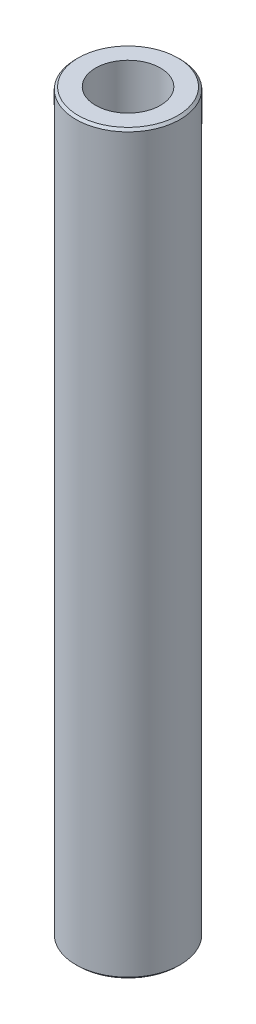
SolidWorks part; units mm, degrees
ref_plane "Front Plane" through (0, 0, 0) normal (0, 0, 1) x (1, 0, 0)
ref_plane "Top Plane" through (0, 0, 0) normal (0, 1, 0) x (1, 0, 0)
ref_plane "Right Plane" through (0, 0, 0) normal (1, 0, 0) x (0, 0, -1)
sketch "Sketch1" plane through (0, 0, 0) normal (0, 1, 0) x (1, 0, 0)
  circle A0 centre (0, 0) radius 42.5
  dimension "SHAFT_OD" = 85
extrude "Boss-Extrude1" add sketch "Sketch1" along normal blind 600
sketch "Sketch2" plane through (0, 0, 0) normal (0, 1, 0) x (1, 0, 0)
  circle A0 centre (0, 0) radius 26.3985
  dimension "BORE_D" = 52.797
extrude "Cut-Extrude1" cut sketch "Sketch2" along normal through all
chamfer "Chamfer1" distance 1.8827 angle 45 2 edges at (0, 600, 42.5) (0, 0, 42.5)
